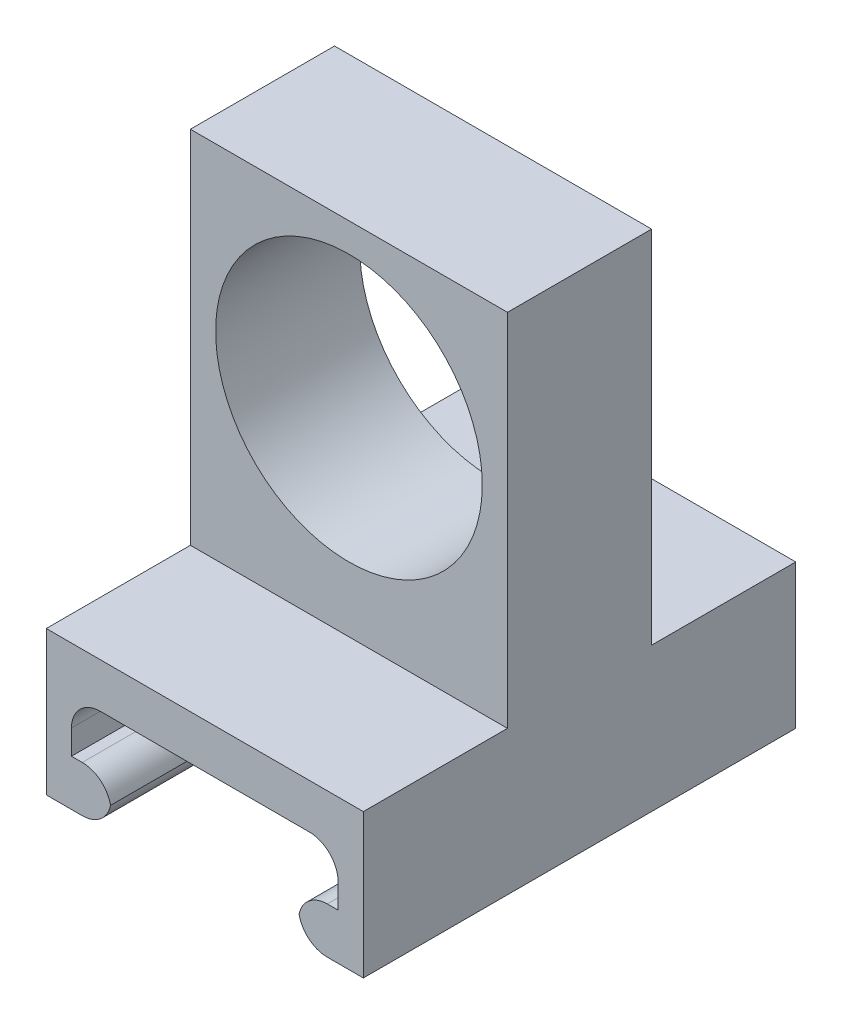
SolidWorks part; units mm, degrees
ref_plane "Front Plane" through (0, 0, 0) normal (0, 0, 1) x (1, 0, 0)
ref_plane "Top Plane" through (0, 0, 0) normal (0, 1, 0) x (1, 0, 0)
ref_plane "Right Plane" through (0, 0, 0) normal (1, 0, 0) x (0, 0, -1)
sketch "Sketch1" plane through (0, 0, 0) normal (0, 1, 0) x (1, 0, 0)
  line L1 (-9.7132, 8.3226) -> (12.2868, 8.3226)
  line L2 (-9.7132, 8.3226) -> (-9.7132, -21.6774)
  line L3 (-9.7132, -21.6774) -> (12.2868, -21.6774)
  line L4 (12.2868, 8.3226) -> (12.2868, -21.6774)
  dimension "D1" = 22
  dimension "D2" = 30
extrude "Boss-Extrude1" add sketch "Sketch1" along normal blind 10
sketch "Sketch2" plane through (0, 0, 21.6774) normal (0, 0, 1) x (1, 0, 0)
  line L0 (-9.7132, 0) -> (12.2868, 0) construction
  line L1 (-7.9632, 6.9) -> (10.5368, 6.9)
  line L2 (-7.9632, 6.9) -> (-7.9632, 3.2)
  line L3 (-7.9632, 3.2) -> (-5.2132, 3.2)
  line L4 (10.5368, 6.9) -> (10.5368, 3.2)
  line L6 (-5.2132, 3.2) -> (-5.2132, 0)
  line L7 (-5.2132, 0) -> (7.7868, 0)
  line L8 (7.7868, 3.2) -> (7.7868, 0)
  line L9 (1.2868, 10) -> (1.2868, 0) construction
  line L10 (-9.7132, 10) -> (12.2868, 10) construction
  line L11 (7.7868, 3.2) -> (10.5368, 3.2)
  point P14 (1.2868, 6.9)
  point P15 (1.2868, 0)
  dimension "D1" = 18.5
  dimension "D2" = 0
  dimension "D3" = 0
  dimension "D4" = 13
  dimension "D5" = 3.7
  dimension "D6" = 3.2
extrude "Cut-Extrude1" cut sketch "Sketch2" against normal through all
fillet "Fillet1" radius 2 6 edges at (-5.2132, 0, 6.6774) (7.7868, 0, 6.6774) (7.7868, 3.2, 6.6774) (-5.2132, 3.2, 6.6774) (10.5368, 6.9, 6.6774) (-7.9632, 6.9, 6.6774)
sketch "Sketch4" plane through (0, 10, 0) normal (0, 1, 0) x (1, 0, 0)
  line L0 (-9.7132, -6.6774) -> (12.2868, -6.6774) construction
  line L1 (-9.7132, 8.3226) -> (-9.7132, -21.6774) construction
  line L2 (12.2868, -21.6774) -> (12.2868, 8.3226) construction
  line L4 (-9.7132, -11.6774) -> (12.2868, -11.6774)
  line L5 (-9.7132, -11.6774) -> (-9.7132, -1.6774)
  line L6 (-9.7132, -1.6774) -> (12.2868, -1.6774)
  line L7 (12.2868, -11.6774) -> (12.2868, -1.6774)
  line L8 (-9.7132, -11.6774) -> (12.2868, -1.6774) construction
  line L9 (-9.7132, -1.6774) -> (12.2868, -11.6774) construction
  point P6 (1.2868, -6.6774)
  dimension "D1" = 10
  dimension "D2" = 0
extrude "Boss-Extrude2" add sketch "Sketch4" along normal blind 25
sketch "Sketch5" plane through (0, 0, 11.6774) normal (0, 0, 1) x (1, 0, 0)
  line L0 (1.2868, 35) -> (1.2868, 10) construction
  line L1 (-9.7132, 35) -> (12.2868, 35) construction
  line L2 (-9.7132, 10) -> (12.2868, 10) construction
  circle A0 centre (1.2868, 23.746) radius 9.25
  dimension "D1" = 18.5
  dimension "D2" = 11.254
extrude "Cut-Extrude2" cut sketch "Sketch5" against normal up to next
